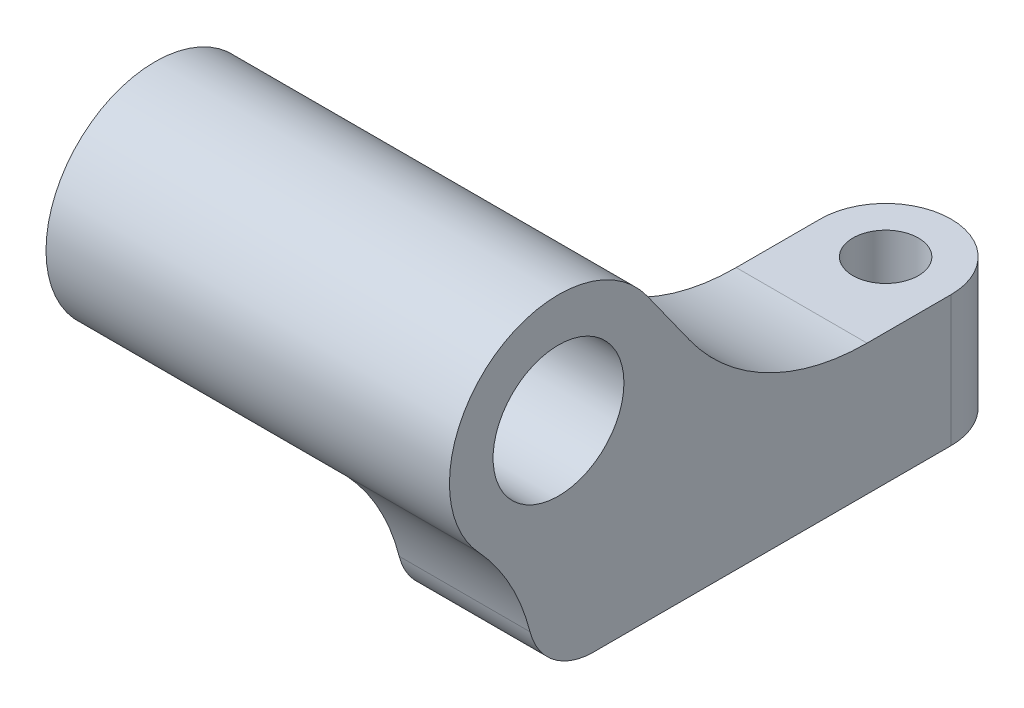
SolidWorks part; units mm, degrees
ref_plane "Plan de face" through (0, 0, 0) normal (0, 0, 1) x (1, 0, 0)
ref_plane "Plan de dessus" through (0, 0, 0) normal (0, 1, 0) x (1, 0, 0)
ref_plane "Plan de droite" through (0, 0, 0) normal (1, 0, 0) x (0, 0, -1)
ref_plane "Plan1" [suppressed] through (10, 0, 0) normal (1, 0, 0) x (0, 0, -1)
sketch "Esquisse1" plane through (0, 0, 0) normal (1, 0, 0) x (0, 0, -1)
  line L0 (-1, -4.899) -> (-1, -10)
  line L1 (-1, -10) -> (16, -10)
  line L2 (16, -10) -> (14, -4)
  line L5 (14, -4) -> (9, -4)
  line L6 (9, -4) -> (4.0691, 2.9055)
  arc A0 (-1, -4.899) -> (4.0691, 2.9055) centre (0, 0) cw
  dimension "D1" = 5
  dimension "D2" = 16
  dimension "D3" = 1
  dimension "D4" = 6
  dimension "D5" = 2
  dimension "D6" = 5
  dimension "D7" = 10
extrude "Boss.-Extru.1" add sketch "Esquisse1" along normal blind 6
fillet "Congé3" radius 10 1 edges at (3, -4.899, 1)
sketch "Esquisse2" plane through (0, 0, 0) normal (-1, 0, 0) x (0, 0, 1)
  circle A0 centre (0, 0) radius 5
extrude "Boss.-Extru.2" add sketch "Esquisse2" along normal blind 12.5
sketch "Esquisse3" plane through (6, 0, 0) normal (1, 0, 0) x (0, 0, -1)
  circle A0 centre (0, 0) radius 3
  dimension "D1" = 6
extrude "Enlèv. mat.-Extru.1" cut sketch "Esquisse3" against normal through all
sketch "Esquisse4" plane through (0, -10, 0) normal (0, -1, 0) x (1, 0, 0)
  line L0 (6, -11) -> (0, -11)
  line L1 (6, 1) -> (6, -16) construction
  line L2 (0, 1) -> (0, -16) construction
  line L3 (0, -11) -> (0, -18)
  line L4 (6, -18) -> (6, -11)
  line L5 (6, -16) -> (0, -16) construction
  arc A0 (0, -18) -> (6, -18) centre (3, -18) ccw
  dimension "D2" = 7
  dimension "D1" = 5
extrude "Boss.-Extru.3" add sketch "Esquisse4" against normal up to surface (6 mm away) up to face at (3, -4, -11.5)
fillet "Congé5" radius 10 1 edges at (3, -4, -9)
sketch "Esquisse5" plane through (0, -4, 0) normal (0, 1, 0) x (1, 0, 0)
  circle A0 centre (3, 18) radius 1.5
  dimension "D1" = 3
extrude "Enlèv. mat.-Extru.2" cut sketch "Esquisse5" against normal through all
fillet "Congé7" radius 3 1 edges at (3, -10, 1)
ref_plane "Plan2" [suppressed] through (15, 0, 0) normal (1, 0, 0) x (0, 0, -1)
mirror "Symétrie1" [suppressed] about plane through (15, 0, 0) normal (1, 0, 0) of bodies 112
delete or keep bodies "Corps-Supprimer/Garder 1" [suppressed] type delete bodies bodies 112
